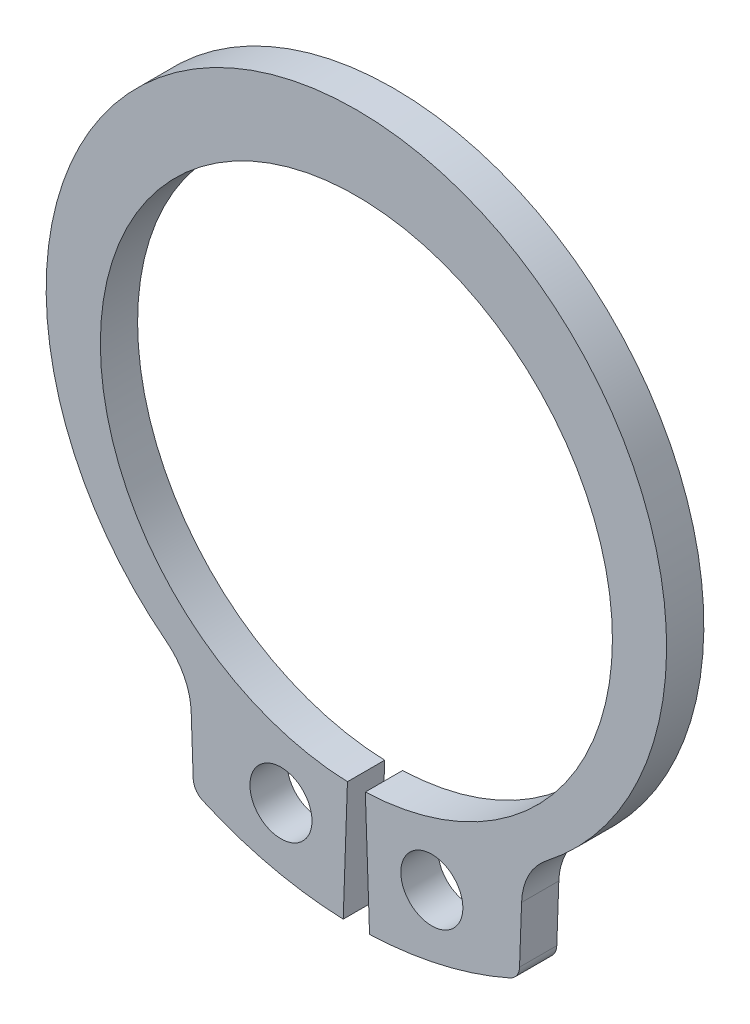
SolidWorks part; units mm, degrees
ref_plane "Front Plane" through (0, 0, 0) normal (0, 0, 1) x (1, 0, 0)
ref_plane "Top Plane" through (0, 0, 0) normal (0, 1, 0) x (1, 0, 0)
ref_plane "Right Plane" through (0, 0, 0) normal (1, 0, 0) x (0, 0, -1)
sketch "Sketch1" plane through (0, 0, 0) normal (0, 0, 1) x (1, 0, 0)
  line L0 (0, 0.01) -> (-7.1447, -4.115) construction
  line L1 (0, 12.15) -> (0, -12.14) construction
  line L2 (-5.2462, -10.9572) -> (-5.3591, -7.7734) construction
  line L3 (0, 10.66) -> (0, 8.26)
  line L4 (-5.3591, -7.7734) -> (-6.0397, -8.7618) construction
  line L5 (-5.3591, -7.7734) -> (0, 0.01) construction
  line L6 (0, 8.26) -> (0, 10.66) construction
  line L7 (0, 10.66) -> (0, 9.46) construction
  line L8 (0, -8.24) -> (0, -12.14) construction
  line L9 (-2.8963, -11.7973) -> (0, 0.01) construction
  line L10 (0, 0.01) -> (-0.4243, -12.14) construction
  line L11 (-5.2462, -10.9572) -> (0, 0.01) construction
  line L12 (-5.3261, -8.7053) -> (-6.1221, -7.2373) construction
  line L13 (-5.7241, -7.9713) -> (-5.3591, -7.7734) construction
  line L14 (-1.9654, -8.0024) -> (-2.8963, -11.7973) construction
  line L15 (-2.4308, -9.8999) -> (-1.4596, -10.1381) construction
  line L16 (-0.4243, -12.14) -> (-0.2879, -8.2349)
  line L17 (-5.2462, -10.9572) -> (-5.3591, -7.7734)
  arc A0 (0, 10.66) -> (-5.3591, -7.7734) centre (0, 0.6643) ccw construction
  circle A2 centre (0, 0.01) radius 10.65 construction
  arc A3 (-5.2462, -10.9572) -> (-0.4243, -12.14) centre (0, 0.01) ccw construction
  circle A4 centre (0, 0.01) radius 8.25 construction
  circle A6 centre (-2.4308, -9.8999) radius 1 construction
  arc A7 (-6.1221, -7.2373) -> (-5.3261, -8.7053) centre (-7.3913, -8.8753) cw construction
  circle A9 centre (0, 0.01) radius 9 construction
  circle A10 centre (0, 0.01) radius 8.5 construction
  circle A11 centre (-2.4308, -9.8999) radius 1
  arc A12 (-0.4243, -12.14) -> (-5.2462, -10.9572) centre (0, 0.01) cw
  arc A13 (0, 8.26) -> (-0.2879, -8.2349) centre (0, 0.01) ccw
  arc A14 (-5.3591, -7.7734) -> (0, 10.66) centre (0, 0.6643) cw
  point P5 (-7.1447, -4.115)
  point P24 (-4.5957, -9.5974)
  point P35 (0, 10.66)
  point P36 (0, 8.26)
  point P37 (0, -8.24)
  point P38 (0, -12.14)
  dimension "Hole Diameter" = 2
  dimension "D10" = 2.0722
  dimension "For OD" = 18
  dimension "ID" = 16.5
  dimension "Max Sec." = 2.4
  dimension "Lug Height" = 3.9
  dimension "D6" = 2
  dimension "D5" = 3.1858
  dimension "D8" = 1.67
  dimension "D3" = 120
  dimension "D2" = 5
  dimension "D4" = 1.67
extrude "Boss-Extrude1" add sketch "Sketch1" along normal blind 1.2
fillet "Fillet1" radius 2.07 1 edges at (-5.3591, -7.7734, 0.6)
fillet "Fillet4" radius 0.52 1 edges at (-5.2462, -10.9572, 0.6)
mirror "Mirror1" about plane through (0, 10.66, 1.2) normal (-1, 0, 0) of "Fillet1", "Fillet4", "Boss-Extrude1"
equation "\"For Groove Diameter@Sketch1\"=\"groove_d\""
equation "\"For OD@Sketch1\"=\"shaft_od\""
equation "\"Max Sec.@Sketch1\"=\"top_width\""
equation "\"ID@Sketch1\"=\"inner_d\""
equation "\"Lug Height@Sketch1\"=\"lug_height\""
equation "\"Hole Diameter@Sketch1\"=\"hole_d\""
equation "\"D3@Sketch1\"=\"angle\""
equation "\"D6@Sketch1\"=\"lug_inner_angle\""
equation "\"D2@Sketch1\"=\"lug_width\""
equation "\"D4@Sketch1\"=\"edge_width2\""
equation "\"D8@Sketch1\"=\"edge_width\""
equation "\"groove_d\"=17.00"
equation "\"shaft_od\"=18.00"
equation "\"inner_d\"=16.50"
equation "\"top_width\"=2.40"
equation "\"lug_height\"=3.90"
equation "\"hole_d\"=2.00"
equation "\"lug_inner_angle\"=2.00"
equation "\"lug_width\"=5.00"
equation "\"lug_height2\"=3.18"
equation "\"lug_radius\"=0.52"
equation "\"edge_width\"=1.67"
equation "\"edge_width2\"=1.67"
equation "\"edge_radius\"=2.07"
equation "\"angle\"=120.00"
equation "\"groove_t\"=1.30"
equation "\"ring_thickness\"=1.20"
equation "\"D1@Boss-Extrude1\"=\"ring_thickness\""
equation "\"D1@Fillet1\"=\"edge_radius\""
equation "\"D1@Fillet4\"=\"lug_radius\""
